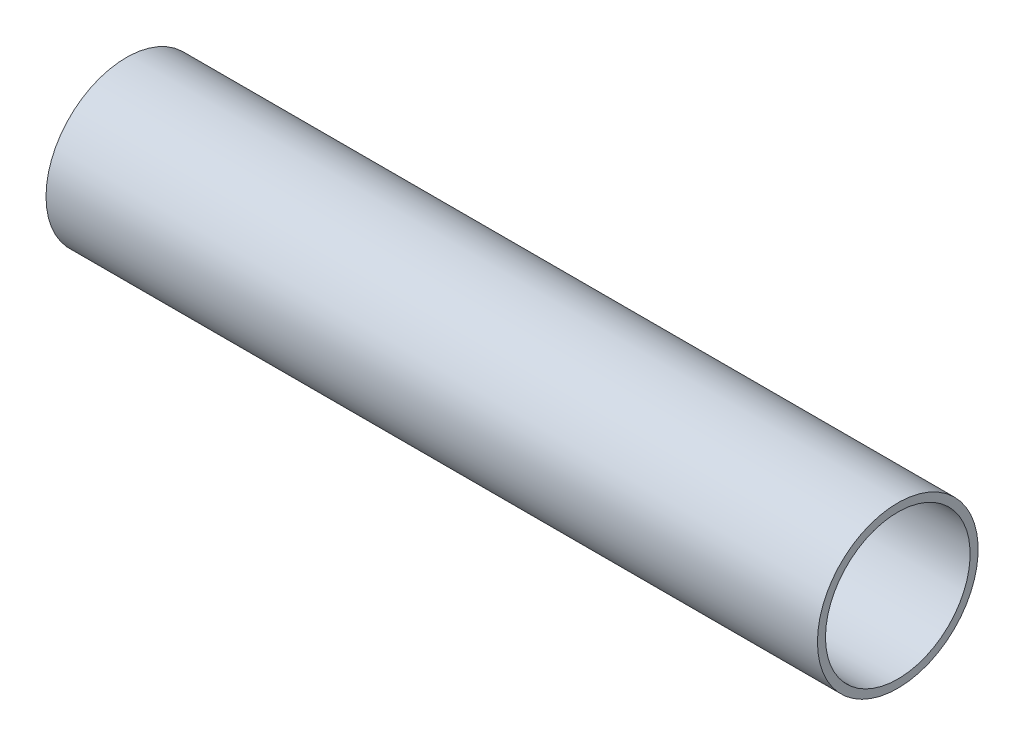
SolidWorks part; units mm, degrees
ref_plane "Front Plane" through (0, 0, 0) normal (0, 0, 1) x (1, 0, 0)
ref_plane "Top Plane" through (0, 0, 0) normal (0, 1, 0) x (1, 0, 0)
ref_plane "Right Plane" through (0, 0, 0) normal (1, 0, 0) x (0, 0, -1)
sketch "Sketch1" plane through (0, 0, 0) normal (1, 0, 0) x (0, 0, -1)
  circle A0 centre (0, 0) radius 14.2875
  circle A1 centre (0, 0) radius 15.875
extrude "Boss-Extrude1" add sketch "Sketch1" along normal mid plane 152.4
